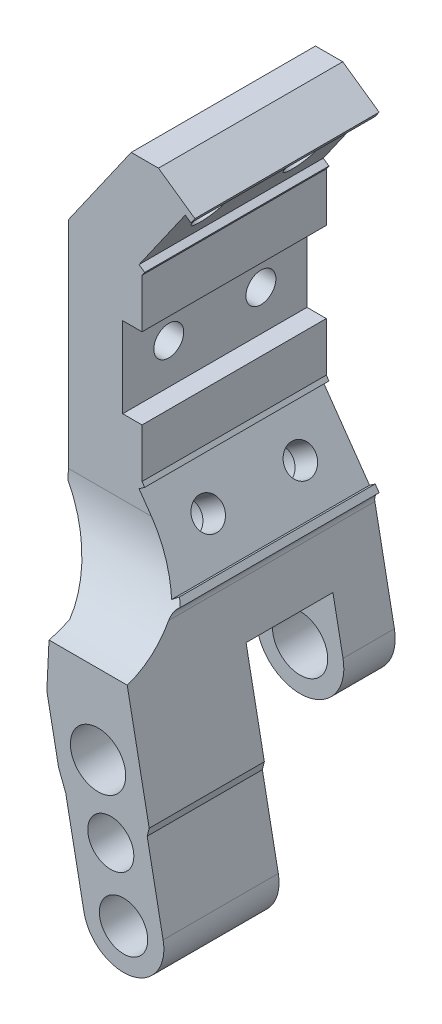
SolidWorks part; units mm, degrees
ref_plane "前视基准面" through (0, 0, 0) normal (0, 0, 1) x (1, 0, 0)
ref_plane "上视基准面" through (0, 0, 0) normal (0, 1, 0) x (1, 0, 0)
ref_plane "右视基准面" through (0, 0, 0) normal (1, 0, 0) x (0, 0, -1)
sketch "草图1" plane through (0, 0, 0) normal (0, 0, 1) x (1, 0, 0)
  line L0 (-28.9767, -151.6119) -> (-4.8865, -186.0162)
  line L1 (6.0233, -52.6473) -> (6.0233, -130.1814)
  line L3 (0.296, 0.1939) -> (-28.9767, -41.6119)
  line L4 (33.8498, -12.9069) -> (-0.3064, -61.687) construction
  line L5 (6.0233, -130.1814) -> (21.0233, -151.6036)
  line L6 (-28.9767, -151.6119) -> (-28.9767, -41.6119)
  line L7 (21.0233, -151.6036) -> (43.6984, -268.2568)
  line L8 (28.9663, -19.8812) -> (6.0233, -52.6473)
  line L9 (-4.8865, -186.0162) -> (12.2863, -274.3627)
  line L10 (-12.377, -147.4811) -> (12.2863, -274.3627) construction
  line L11 (19.0351, -141.3752) -> (43.6984, -268.2568) construction
  line L14 (28.9663, -19.8812) -> (0.296, 0.1939)
  line L17 (5.1795, 7.1683) -> (-28.9767, -41.6119) construction
  arc A0 (12.2863, -274.3627) -> (43.6984, -268.2568) centre (27.9923, -271.3097) ccw
  circle A1 centre (16.9254, -214.3754) radius 12
  dimension "D12" = 90
  dimension "D8" = 50
  dimension "D10" = 16
  dimension "D13" = 58
  dimension "D16" = 42
  dimension "D11" = 16
  dimension "D2" = 0
  dimension "D3" = 35
  dimension "D4" = 35
  dimension "D5" = 35
  dimension "D6" = 11
  dimension "D7" = 35
  dimension "D9" = 110
  dimension "D14" = 40
extrude "拉伸1" add sketch "草图1" along normal blind 110
ref_plane "基准面1" through (0, 0, 85) normal (0, 0, 1) x (1, 0, 0)
ref_plane "基准面2" through (0, 0, 85) normal (0, 0, 1) x (1, 0, 0)
sketch "草图79" plane through (0, 0, 110) normal (0, 0, 1) x (1, 0, 0)
  circle A0 centre (27.9923, -271.3097) radius 10.5
extrude "切除-拉伸45" cut sketch "草图79" against normal blind 120
sketch "草图84" plane through (0, 0, 110) normal (0, 0, 1) x (1, 0, 0)
  line L0 (43.6984, -268.2568) -> (21.0233, -151.6036) construction
  line L1 (33.7789, -180.5395) -> (44.2731, -234.5274)
  line L2 (21.0233, -151.6036) -> (37.4017, -235.8631)
  line L3 (5.9896, -241.969) -> (3.0447, -242.5414)
  line L4 (21.0233, -151.6036) -> (30.8946, -165.7013)
  line L5 (3.0447, -242.5414) -> (-9.1171, -179.9744)
  line L6 (33.7789, -180.5395) -> (30.8946, -165.7013)
  line L7 (-4.8865, -186.0162) -> (-9.1171, -179.9744)
  line L10 (37.4017, -235.8631) -> (44.2731, -234.5274)
  line L12 (-4.8865, -186.0162) -> (12.2863, -274.3627) construction
  line L13 (5.9896, -241.969) -> (-4.169, -189.7075)
  line L14 (-4.8865, -186.0162) -> (-4.169, -189.7075)
  circle A1 centre (16.9254, -214.3754) radius 12 construction
  dimension "D3" = 25
  dimension "D2" = 3
  dimension "D4" = 7
  dimension "D5" = 90
  dimension "D6" = 24
extrude "拉伸2" add sketch "草图84" against normal blind 110
sketch "草图87" plane through (-8.138, -1.5819, 0) normal (0.9816, 0.1908, 0) x (0, 0, -1)
  line L0 (-60, -287.6662) -> (-60, -190.6662)
  line L1 (-110, -287.6662) -> (0, -287.6662) construction
  line L2 (-60, -190.6662) -> (-22.3, -190.6662)
  line L3 (-22.3, -190.6662) -> (-22.3, -287.6662)
  line L4 (-22.3, -287.6662) -> (-60, -287.6662)
  line L6 (-110, -238.6662) -> (-110, -168.5519) construction
  line L9 (0, -238.6662) -> (0, -168.5519) construction
  dimension "D1" = 22.3
  dimension "D2" = 50
  dimension "D3" = 97
extrude "切除-拉伸46" cut sketch "草图87" against normal blind 89 and the other way blind 89
sketch "草图91" plane through (0, 0, 0) normal (0, 0, -1) x (-1, 0, 0)
  line L0 (-27.2456, -22.3387) -> (-24.7881, -20.618)
  line L1 (-6.0233, -52.6473) -> (-28.9663, -19.8812) construction
  line L2 (-24.7881, -20.618) -> (-4.713, -49.2883)
  line L3 (-4.713, -49.2883) -> (-7.1704, -51.009)
  line L4 (-7.1704, -51.009) -> (-27.2456, -22.3387)
  line L5 (-28.9663, -19.8812) -> (-0.296, 0.1939) construction
  line L8 (-7.1704, -131.8197) -> (-27.2456, -160.49)
  line L9 (-4.713, -133.5404) -> (-7.1704, -131.8197)
  line L10 (-24.7881, -162.2107) -> (-4.713, -133.5404)
  line L11 (-27.2456, -160.49) -> (-24.7881, -162.2107)
  dimension "D1" = 35
  dimension "D2" = 3
  dimension "D3" = 3
extrude "切除-拉伸48" cut sketch "草图91" against normal blind 239
sketch "草图92" plane through (0, 0, 110) normal (0, 0, 1) x (1, 0, 0)
  line L2 (6.0233, -73.9143) -> (-2.3767, -73.9143)
  line L3 (6.0233, -108.9143) -> (-2.3767, -108.9143)
  line L5 (6.0233, -73.9143) -> (6.0233, -108.9143)
  line L6 (-2.3767, -130.1814) -> (-2.3767, -52.6473)
  line L7 (-2.3767, -108.9143) -> (-2.3767, -73.9143)
  dimension "D1" = 8.4
  dimension "D2" = 35
  dimension "D3" = 8.4
extrude "切除-拉伸49" cut sketch "草图92" against normal blind 239
sketch "草图93" plane through (26.3204, -18.4297, 0) normal (0.8192, -0.5736, 0) x (0, 0, -1)
  line L1 (-110, -2.6713) -> (0, -2.6713) construction
  line L2 (0, 0.3287) -> (0, -50.7068) construction
  circle A1 centre (-60, -20.1713) radius 6.5
  circle A2 centre (-20, -20.1713) radius 6.5
  dimension "D4" = 13
  dimension "D5" = 17.5
  dimension "D1" = 40
  dimension "D2" = 17.5
  dimension "D6" = 20
extrude "切除-拉伸50" cut sketch "草图93" against normal blind 239
sketch "草图94" plane through (0.1075, -0.0753, 0) normal (-0.8192, 0.5736, 0) x (0, 0, 1)
  line L0 (0, 0.3287) -> (0, -50.7068) construction
  line L1 (110, 0.3287) -> (0, 0.3287) construction
  circle A1 centre (60, -20.1713) radius 10
  circle A2 centre (20, -20.1713) radius 10
  circle A3 centre (100, -20.1713) radius 10 [skipped]
  dimension "D1" = 20
  dimension "D2" = 20.5
  dimension "D3" = 40
  dimension "D4" = 20
extrude "切除-拉伸51" cut sketch "草图94" against normal blind 20
sketch "草图95" plane through (-59.581, -41.7191, 0) normal (0.8192, 0.5736, 0) x (0, 0, -1)
  line L2 (0, -107.5728) -> (0, -142.197) construction
  line L4 (0, -147.0931) -> (-110, -147.0931) construction
  circle A1 centre (-60, -129.5931) radius 6.5
  circle A2 centre (-20, -129.5931) radius 6.5
  circle A3 centre (-100, -129.5931) radius 6.5 [skipped]
  dimension "D3" = 20
  dimension "D1" = 40
  dimension "D4" = 17.5
  dimension "D5" = 13
extrude "切除-拉伸52" cut sketch "草图95" against normal blind 62
sketch "草图96" plane through (-90.6779, -63.4934, 0) normal (-0.8192, -0.5736, 0) x (0, 0, 1)
  circle A0 centre (20, -129.5931) radius 10
  circle A1 centre (60, -129.5931) radius 10
  circle A3 centre (100, -129.5931) radius 10 [skipped]
  dimension "D1" = 20
  dimension "D2" = 40
extrude "切除-拉伸53" cut sketch "草图96" against normal blind 26
sketch "草图97" plane through (-2.3767, 0, 0) normal (1, 0, 0) x (0, 0, -1)
  line L2 (0, -41.6119) -> (0, -151.6119) construction
  line L3 (-110, -73.9143) -> (0, -73.9143) construction
  circle A1 centre (-60, -91.4143) radius 6.5
  circle A2 centre (-20, -91.4143) radius 6.5
  circle A3 centre (-100, -91.4143) radius 6.5 [skipped]
  dimension "D3" = 20
  dimension "D1" = 40
  dimension "D4" = 17.5
extrude "切除-拉伸54" cut sketch "草图97" against normal blind 52
chamfer "倒角3" distance 15 angle 25 1 edges at (44.2731, -234.5274, 85) first distance on face at (38.6387, -205.5414, 48.075)
sketch "草图100" plane through (0, 0, 0) normal (0, 0, -1) x (-1, 0, 0)
  line L0 (-44.2731, -234.5274) -> (6.1852, -243.4246)
  line L1 (6.1852, -243.4246) -> (-1.3935, -301.9029)
  line L2 (-1.3935, -301.9029) -> (-49.1634, -290.6573)
  line L3 (-49.1634, -290.6573) -> (-44.2731, -234.5274)
extrude "切除-拉伸56" cut sketch "草图100" against normal blind 40
chamfer "倒角4" distance 17 angle 10 1 edges at (3.0447, -242.5414, 85) first distance on face at (-2.3204, -214.9402, 48.075)
sketch "草图101" plane through (-28.9767, 0, 0) normal (-1, 0, 0) x (0, 0, 1)
  line L0 (80, 0.1939) -> (80, -179.9744)
  line L2 (110, 0.1939) -> (0, 0.1939) construction
  line L3 (0, -179.9744) -> (110, -179.9744) construction
  line L4 (80, -179.9744) -> (110, -179.9744)
  line L5 (110, -179.9744) -> (110, 0.1939)
  line L6 (110, 0.1939) -> (80, 0.1939)
  line L8 (0, -41.6119) -> (0, -151.6119) construction
  dimension "D1" = 80
extrude "切除-拉伸57" cut sketch "草图101" against normal blind 100
sketch "草图104" plane through (0, 0, 0) normal (0, 0, -1) x (-1, 0, 0)
  line L2 (-32.2372, -193.5715) -> (-38.9155, -227.9285)
  line L3 (-38.9155, -227.9285) -> (-40.3332, -235.2221)
  line L5 (-28.9663, -162.9474) -> (-32.2372, -193.5715)
  line L6 (-44.2731, -234.5274) -> (-40.3332, -235.2221)
  line L11 (-44.2731, -234.5274) -> (-30.8946, -165.7013)
  line L12 (-30.8946, -165.7013) -> (-28.9663, -162.9474)
extrude "切除-拉伸60" cut sketch "草图104" against normal through all
sketch "草图105" plane through (0, 0, 0) normal (0, 0, -1) x (-1, 0, 0)
  line L1 (-20.5508, -233.0263) -> (19.1754, -240.7483)
  line L2 (-20.5508, -233.0263) -> (-58.4023, -225.6687)
  line L3 (-58.4023, -225.6687) -> (-58.4023, -238.9471)
  line L4 (-58.4023, -238.9471) -> (4.5305, -248.7214)
  line L5 (4.5305, -248.7214) -> (19.1754, -240.7483)
extrude "切除-拉伸61" cut sketch "草图105" against normal blind 30
fillet "圆角5" radius 19 2 edges at (1.8999, -236.6517, 11.15) (39.2017, -229.4009, 11.15)
sketch "草图106" plane through (0, 0, 0) normal (0, 0, -1) x (-1, 0, 0)
  circle A1 centre (-14.0633, -199.651) radius 2
  circle A2 centre (-19.7875, -229.0998) radius 2
extrude "切除-拉伸62" cut sketch "草图106" against normal blind 10
sketch "草图108" plane through (0, 0, 60) normal (0, 0, -1) x (-1, 0, 0)
  line L0 (-38.2641, -232.4244) -> (-37.4017, -235.8631)
  line L1 (-45.1708, -267.9706) -> (-38.2641, -232.4244)
  line L2 (-5.9896, -241.969) -> (-12.2863, -274.3627)
  line L3 (-37.4017, -235.8631) -> (-43.6984, -268.2568)
  line L4 (-10.8138, -274.6489) -> (-3.4359, -236.6926)
  line L6 (-3.4359, -236.6926) -> (-2.8959, -233.9144)
  line L7 (-39.1212, -228.9867) -> (-37.4069, -235.8621) construction
  line L8 (-5.9896, -241.969) -> (-2.8959, -233.9144)
  arc A0 (-45.1708, -267.9706) -> (-10.8138, -274.6489) centre (-27.9923, -271.3097) ccw
  arc A1 (-43.6984, -268.2568) -> (-12.2863, -274.3627) centre (-27.9923, -271.3097) ccw
  dimension "D1" = 1.5
  dimension "D2" = 17.5
extrude "拉伸3" add sketch "草图108" against normal blind 50
sketch "草图109" plane through (0, 0, 0) normal (0, 0, -1) x (-1, 0, 0)
  line L0 (28.9767, -41.6119) -> (31.9767, -45.8963)
  line L1 (28.9767, -151.6119) -> (31.9767, -147.3274)
  line L3 (28.9767, -41.6119) -> (28.9767, -151.6119)
  line L4 (31.9767, -41.6119) -> (31.9767, -151.6119)
  line L5 (31.9767, -45.8963) -> (31.9767, -147.3274)
  dimension "D1" = 3
extrude "拉伸4" add sketch "草图109" against normal blind 80
sketch "草图110" plane through (-2.3767, 0, 0) normal (1, 0, 0) x (0, 0, -1)
  circle A0 centre (-60, -91.4143) radius 6.5
  circle A1 centre (-20, -91.4143) radius 6.5
extrude "切除-拉伸63" cut sketch "草图110" against normal blind 80
sketch "草图111" plane through (-31.9767, 0, 0) normal (-1, 0, 0) x (0, 0, 1)
  circle A0 centre (20, -91.4143) radius 10
  circle A1 centre (60, -91.4143) radius 10
  dimension "D1" = 20
extrude "切除-拉伸64" cut sketch "草图111" against normal blind 18
fillet "圆角7" radius 40 1 edges at (10.8339, -179.9744, 80)
sketch "草图112" plane through (0, 0, 0) normal (0, 0, -1) x (-1, 0, 0)
  line L6 (-5.2109, -3.2475) -> (-0.296, 0.1939)
  line L7 (-0.296, 0.1939) -> (31.9767, -45.8963)
  line L8 (31.9767, -45.8963) -> (31.9767, -147.3274)
  line L9 (25.9767, -145.4356) -> (4.2022, -176.5329)
  line L10 (-5.2109, -3.2475) -> (25.9767, -47.7881)
  line L11 (25.9767, -47.7881) -> (25.9767, -145.4356)
  line L12 (25.9767, -145.4356) -> (4.2022, -176.5329)
  line L13 (-5.2109, -3.2475) -> (25.9767, -47.7881)
  line L14 (25.9767, -47.7881) -> (25.9767, -145.4356)
  line L15 (31.9767, -147.3274) -> (9.1171, -179.9744)
  line L16 (9.1171, -179.9744) -> (4.2022, -176.5329)
  dimension "D1" = 6
extrude "切除-拉伸65" cut sketch "草图112" against normal through all
sketch "草图113" plane through (0, 0, 0) normal (0, 0, -1) x (-1, 0, 0)
  line L0 (4.2022, -176.5329) -> (5.3009, -199.6069)
  line L1 (9.1171, -179.9744) -> (1.7255, -218.0007) construction
  line L2 (5.3009, -199.6069) -> (9.1171, -179.9744)
  line L3 (9.1171, -179.9744) -> (4.2022, -176.5329)
  dimension "D1" = 20
extrude "切除-拉伸66" cut sketch "草图113" against normal through all
sketch "草图114" plane through (0, 0, 110) normal (0, 0, 1) x (1, 0, 0)
  circle A0 centre (22.4589, -242.8426) radius 10
extrude "切除-拉伸67" cut sketch "草图114" against normal through all
sketch "草图116" plane through (0, 0, 80) normal (0, 0, 1) x (1, 0, 0)
  line L1 (27.9923, -8.8097) -> (-43.3134, -8.8097)
  line L2 (-43.3134, -8.8097) -> (15.8908, 7.7284)
  line L3 (15.8908, 7.7284) -> (27.9923, -8.8097)
extrude "切除-拉伸68" cut sketch "草图116" against normal through all
sketch "草图117" plane through (0, 0, 0) normal (0, 0, -1) x (-1, 0, 0)
  line L0 (-32.2372, -193.5715) -> (-26.8736, -165.9783)
  line L1 (-28.9663, -162.9474) -> (-26.6057, -164.6003)
  line L2 (-26.8736, -165.9783) -> (-26.6057, -164.6003)
  line L3 (-28.9663, -162.9474) -> (-32.2372, -193.5715)
extrude "切除-拉伸69" cut sketch "草图117" against normal through all
fillet "圆角8" radius 4 1 edges at (26.6057, -164.6003, 43.7634)
